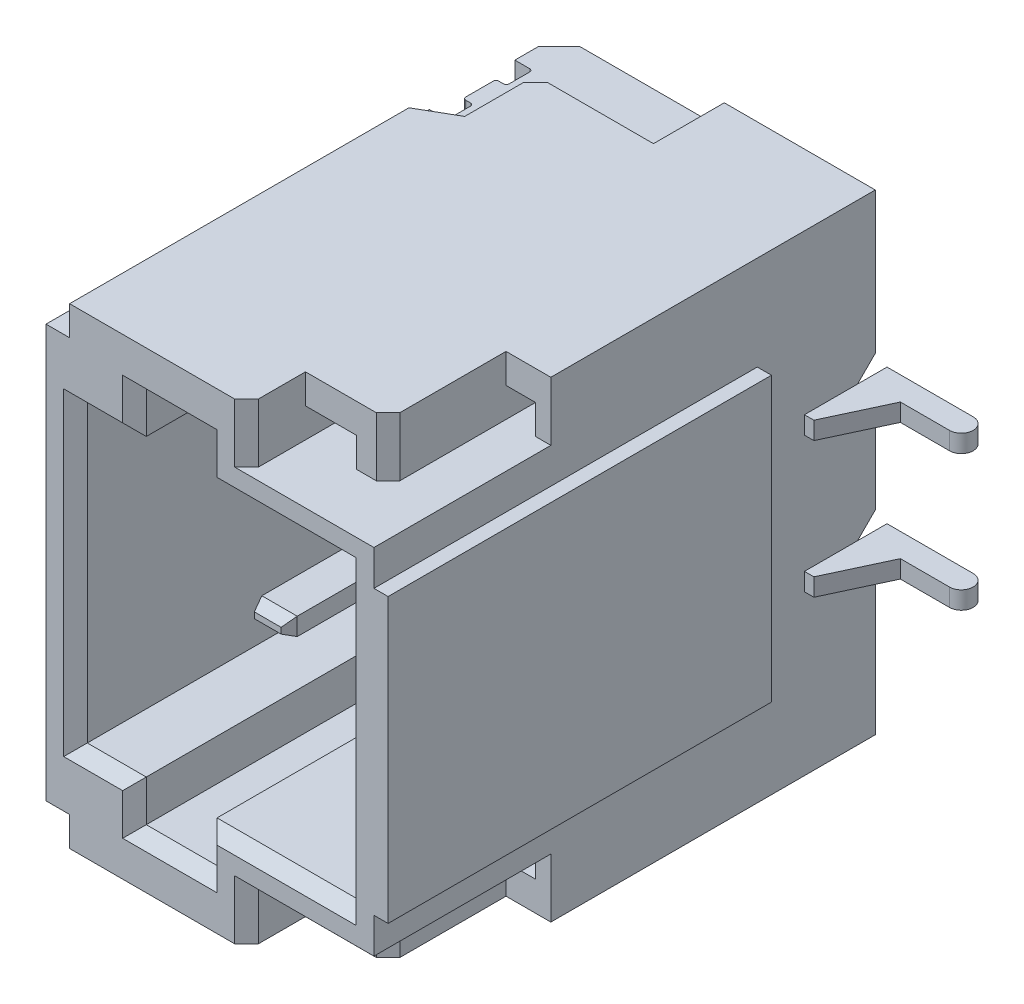
SolidWorks part; units mm, degrees
ref_plane "Front Plane" through (0, 0, 0) normal (0, 0, 1) x (1, 0, 0)
ref_plane "Top Plane" through (0, 0, 0) normal (0, 1, 0) x (1, 0, 0)
ref_plane "Right Plane" through (0, 0, 0) normal (1, 0, 0) x (0, 0, -1)
sketch "Sketch2" plane through (0, 0, 0) normal (0, 1, 0) x (1, 0, 0)
  line L0 (22.6306, -2.3603) -> (22.6306, -1.9103)
  line L1 (22.6306, -1.9103) -> (25.4106, -1.9103)
  line L2 (25.4106, -1.9103) -> (25.4106, -1.6603)
  line L3 (25.4106, -1.6603) -> (26.1406, -1.6603)
  line L4 (26.1406, -1.8603) -> (25.7238, -1.8603)
  line L5 (25.7238, -1.8603) -> (25.4906, -2.3603)
  line L6 (25.4906, -2.3603) -> (22.6306, -2.3603)
  arc A0 (26.1406, -1.8603) -> (26.1406, -1.6603) centre (26.1406, -1.7603) ccw
extrude "Boss-Extrude2" add sketch "Sketch2" along normal blind 0.15 from offset 0.815 separate body contours L6 L0 L1 L2 L3 A0 L4 L5 offset against normal yes
sketch "Sketch3" plane through (0, 0, 0) normal (0, 1, 0) x (1, 0, 0)
  line L0 (22.7306, -2.9603) -> (24.1306, -2.9603)
  line L1 (24.1306, -2.9603) -> (24.1306, -1.8353)
  line L2 (24.1306, -1.8353) -> (23.9556, -1.6603)
  line L3 (23.9556, -1.6603) -> (22.8056, -1.6603)
  line L4 (22.8056, -1.6603) -> (22.6306, -1.8353)
  line L5 (22.6306, -1.8353) -> (22.6306, -2.0353)
  line L6 (22.6306, -2.0353) -> (22.7556, -2.0353)
  line L7 (22.7806, -2.2328) -> (22.7806, -2.0603)
  line L8 (22.6306, -2.7603) -> (22.6306, -2.8603)
  line L9 (22.6306, -2.8603) -> (22.7306, -2.9603)
  line L10 (22.6306, -2.7603) -> (22.7556, -2.7603)
  line L11 (22.7806, -2.7353) -> (22.7806, -2.5628)
  line L12 (22.7181, -2.5378) -> (22.7556, -2.5378)
  line L13 (22.6931, -2.2828) -> (22.6931, -2.5128)
  line L14 (22.7181, -2.2578) -> (22.7556, -2.2578)
  arc A0 (22.7556, -2.7603) -> (22.7806, -2.7353) centre (22.7556, -2.7353) ccw
  arc A1 (22.7806, -2.5628) -> (22.7556, -2.5378) centre (22.7556, -2.5628) ccw
  arc A2 (22.7181, -2.5378) -> (22.6931, -2.5128) centre (22.7181, -2.5128) cw
  arc A3 (22.7556, -2.0353) -> (22.7806, -2.0603) centre (22.7556, -2.0603) cw
  arc A4 (22.7556, -2.2578) -> (22.7806, -2.2328) centre (22.7556, -2.2328) ccw
  arc A5 (22.7181, -2.2578) -> (22.6931, -2.2828) centre (22.7181, -2.2828) ccw
extrude "Boss-Extrude3" add sketch "Sketch3" along normal blind 0.2 from offset 2.26 separate body contours L0 L1 L2 L3 L4 L5 L6 A3 L7 A4 L14 A5 L13 A2 L12 A1 L11 A0 L10 L8 L9
sketch "Sketch4" plane through (0, 0, 0) normal (0, 0, 1) x (1, 0, 0)
  line L0 (25.5306, -3.2409) -> (22.6306, -3.2409)
  line L1 (22.6306, -3.2409) -> (22.6306, 2.7591)
  line L2 (25.5306, 2.7591) -> (22.6306, 2.7591)
  line L3 (25.5306, -3.2409) -> (25.5306, 2.7591)
extrude "Boss-Extrude4" add sketch "Sketch4" along normal blind 4.25 from offset 1.76 separate body
sketch "Sketch6" plane through (25.5306, 0, 0) normal (1, 0, 0) x (0, 0, -1)
  line L0 (-2.7603, -2.4409) -> (-2.7603, 1.9591)
  line L1 (-2.7603, 1.9591) -> (-6.161, 1.9591)
  line L2 (-6.161, 1.9591) -> (-6.161, -2.4409)
  line L3 (-6.161, -2.4409) -> (-2.7603, -2.4409)
extrude "Cut-Extrude3" cut sketch "Sketch6" against normal blind 0.12 flip side to cut
sketch "Sketch7" plane through (0, 0, 6.01) normal (0, 0, 1) x (1, 0, 0)
  line L0 (22.8806, -2.4909) -> (25.1606, -2.4909)
  line L1 (25.1606, -2.4909) -> (25.1606, 2.0091)
  line L2 (25.1606, 2.0091) -> (22.8806, 2.0091)
  line L3 (22.8806, 2.0091) -> (22.8806, -2.4909)
extrude "Cut-Extrude4" cut sketch "Sketch7" against normal blind 3.2
sketch "Sketch8" plane through (0, 0, 6.01) normal (0, 0, 1) x (1, 0, 0)
  line L0 (23.3806, 2.0091) -> (23.9806, 2.0091)
  line L1 (23.9806, 2.0091) -> (23.9806, 2.3591)
  line L2 (23.9806, 2.3591) -> (23.3806, 2.3591)
  line L3 (23.3806, 2.3591) -> (23.3806, 2.0091)
  line L4 (23.3806, -2.4909) -> (23.9806, -2.4909)
  line L5 (23.9806, -2.4909) -> (23.9806, -2.8409)
  line L6 (23.9806, -2.8409) -> (23.3806, -2.8409)
  line L7 (23.3806, -2.8409) -> (23.3806, -2.4909)
extrude "Cut-Extrude6" cut sketch "Sketch8" against normal blind 2.6
chamfer "Chamfer1" distance 0.1 angle 45 12 edges at (22.8806, -0.2409, 6.01) (23.1306, -2.4909, 6.01) (23.3806, -2.6659, 6.01) (23.6806, -2.8409, 6.01) (23.9806, -2.6659, 6.01) (24.5706, -2.4909, 6.01) (25.1606, -0.2409, 6.01) (24.5706, 2.0091, 6.01) (23.9806, 2.1841, 6.01) (23.6806, 2.3591, 6.01) (23.3806, 2.1841, 6.01) (23.1306, 2.0091, 6.01)
sketch "Sketch9" plane through (0, 0, 0) normal (0, 1, 0) x (1, 0, 0)
  line L0 (23.3606, -2.8103) -> (23.6606, -2.8103)
  line L1 (23.6606, -2.8103) -> (23.6606, -4.9103)
  line L2 (23.6606, -4.9103) -> (23.6242, -5.0103)
  line L3 (23.6242, -5.0103) -> (23.397, -5.0103)
  line L4 (23.397, -5.0103) -> (23.3606, -4.9103)
  line L5 (23.3606, -4.9103) -> (23.3606, -2.8103)
extrude "Boss-Extrude5" add sketch "Sketch9" along normal blind 0.15 from offset 1.82 separate body offset against normal yes
chamfer "Chamfer2" distance 0.1 distance2 0.05 1 edges at (23.5106, -1.82, 5.0103) first distance on face at (23.5106, -1.82, 4.2436)
chamfer "Chamfer3" distance 0.05 distance2 0.1 1 edges at (23.5106, -1.67, 5.0103) first distance on face at (23.5106, -1.72, 5.0103)
sketch "Sketch10" plane through (22.6306, 0, 0) normal (-1, 0, 0) x (0, 0, 1)
  line L0 (6.0103, 2.5091) -> (6.0103, 2.7591)
  line L1 (6.0103, 2.7591) -> (1.4717, 2.7591)
  line L2 (1.4717, 2.7591) -> (1.4717, 2.5091)
  line L3 (1.4717, 2.5091) -> (6.0103, 2.5091)
  line L4 (6.0103, -3.2409) -> (6.0103, -2.9909)
  line L5 (6.0103, -2.9909) -> (1.2054, -2.9909)
  line L6 (1.2054, -2.9909) -> (1.2054, -3.2409)
  line L7 (1.2054, -3.2409) -> (6.0103, -3.2409)
extrude "Cut-Extrude7" cut sketch "Sketch10" against normal blind 0.2
sketch "Sketch11" plane through (0, -3.2409, 0) normal (0, -1, 0) x (1, 0, 0)
  line L0 (22.6306, 3.249) -> (23.1306, 2.9603)
  line L1 (23.1306, 2.9603) -> (23.1306, 2.3603)
  line L2 (23.1306, 2.3603) -> (24.1306, 2.3603)
  line L3 (24.1306, 2.3603) -> (24.1306, 1.6436)
  line L4 (24.1306, 1.6436) -> (22.6306, 1.6436)
  line L5 (22.6306, 1.6436) -> (22.6306, 3.249)
extrude "Cut-Extrude8" cut sketch "Sketch11" against normal blind 0.5
sketch "Sketch12" plane through (23.1306, 0, 0) normal (-1, 0, 0) x (0, 0, 1)
  line L0 (2.9603, -2.9909) -> (2.9603, -2.7409)
  line L1 (2.9603, -2.7409) -> (2.9603, -3.2409) construction
  line L2 (2.9603, -2.7409) -> (2.3603, -2.7409)
  line L3 (2.3603, -2.7409) -> (2.3603, -2.9909)
  line L4 (2.3603, -2.7409) -> (2.3603, -3.2409) construction
  line L5 (2.3603, -2.9909) -> (2.9603, -2.9909)
extrude "Cut-Extrude9" cut sketch "Sketch12" against normal up to surface (1 mm away) up to face at (24.1306, -2.9909, 2.0601)
chamfer "Chamfer4" distance 0.1 angle 45 1 edges at (22.6306, -2.7409, 2.5045)
chamfer "Chamfer5" distance 0.1 angle 45 1 edges at (23.1306, -3.1159, 2.3603)
ref_plane "Plane1" through (0, -0.2409, 0) normal (0, -1, 0) x (-1, 0, 0)
mirror "Mirror1" about plane through (0, -0.2409, 0) normal (0, -1, 0) of "Chamfer5", "Cut-Extrude8", "Chamfer4", "Cut-Extrude9"
mirror "Mirror2" about plane through (0, -0.2409, 0) normal (0, -1, 0) of bodies 128
sketch "Sketch13" plane through (0, -3.2409, 0) normal (0, -1, 0) x (1, 0, 0)
  line L0 (24.3306, 5.5103) -> (24.3306, 6.0696)
  line L1 (25.0306, 4.5103) -> (25.671, 4.5103)
  line L2 (25.0306, 4.5103) -> (25.0306, 5.5103)
  line L3 (24.3306, 5.5103) -> (25.0306, 5.5103)
  line L4 (25.671, 4.5103) -> (25.671, 6.0696)
  line L5 (25.671, 6.0696) -> (24.3306, 6.0696)
  point P0 (24.3306, 5.5103)
  point P1 (25.0306, 4.5103)
  point P8 (25.0306, 5.4103)
extrude "Cut-Extrude10" cut sketch "Sketch13" against normal blind 0.5
chamfer "Chamfer6" distance 0.1 angle 45 2 edges at (24.3306, -2.9909, 6.01) (25.0306, -2.9909, 5.5103)
sketch "Sketch14" plane through (0, 0, 5.5103) normal (0, 0, 1) x (1, 0, 0)
  line L0 (24.3306, -2.7409) -> (24.3306, -2.9909)
  line L1 (24.3306, -2.7409) -> (24.3306, -3.2409) construction
  line L2 (24.3306, -2.9909) -> (24.7617, -2.9909)
  line L3 (24.7617, -2.9909) -> (24.7617, -2.7409)
  line L4 (24.3306, -2.7409) -> (24.9306, -2.7409) construction
  line L5 (24.7617, -2.7409) -> (24.3306, -2.7409)
  line L6 (25.0306, -2.7409) -> (25.0306, -2.9909)
  line L7 (25.0306, -2.7409) -> (25.0306, -3.2409) construction
  line L8 (25.0306, -2.9909) -> (25.2818, -2.9909)
  line L9 (25.2818, -2.9909) -> (25.2818, -2.7409)
  line L10 (25.0306, -2.7409) -> (25.4106, -2.7409) construction
  line L11 (25.2818, -2.7409) -> (25.0306, -2.7409)
extrude "Cut-Extrude11" cut sketch "Sketch14" against normal blind 2
mirror "Mirror3" about plane through (0, -0.2409, 0) normal (0, -1, 0) of "Chamfer6", "Cut-Extrude10", "Cut-Extrude11"
sketch "Szkic1" plane through (22.6306, 0, 0) normal (-1, 0, 0) x (0, 0, 1)
  line L0 (1.76, -0.2409) -> (6.1352, -0.2409) construction
  line L1 (1.76, 2.1591) -> (1.76, -2.6409) construction
  line L3 (1.4476, -1.2409) -> (6.4476, -1.2409)
  line L4 (1.4476, -1.2409) -> (1.4476, 0.7591)
  line L5 (1.4476, 0.7591) -> (6.4476, 0.7591)
  line L6 (6.4476, -1.2409) -> (6.4476, 0.7591)
  line L7 (1.4476, -1.2409) -> (6.4476, 0.7591) construction
  line L8 (1.4476, 0.7591) -> (6.4476, -1.2409) construction
  point P4 (3.9476, -0.2409)
  dimension "D1" = 2
  dimension "D2" = 5
extrude "Wytnij-wyciągnięcie1" cut sketch "Szkic1" against normal through all
move or copy body "Obiekt-Przenieś/Kopiuj1" bodies to move or copy 147 128 copy no translate (0, -2, 0) parameters "D1"=0, "D2"=2, "D3"=0
combine bodies "Połącz1" operation type add bodies to combine 149 148
sketch "Sketch5" plane through (22.6306, 0, 0) normal (-1, 0, 0) x (0, 0, 1)
  line L0 (1.7603, -0.4409) -> (1.9103, -0.5909)
  line L1 (1.9103, -0.5909) -> (2.3603, -0.5909)
  line L2 (2.3603, -0.5909) -> (2.3603, -0.7409)
  line L3 (2.3603, -0.7409) -> (1.9103, -0.7409)
  line L4 (1.9103, -0.7409) -> (1.7603, -0.8909)
  line L6 (1.7603, -0.4409) -> (1.7527, -0.4409)
  line L7 (1.7527, -0.4409) -> (1.7527, -0.8909)
  line L8 (1.7527, -0.8909) -> (1.7603, -0.8909)
  line L9 (1.76, -1.2409) -> (2.7788, -1.2409) construction
  line L10 (1.76, 0.1591) -> (1.76, -2.6409) construction
  line L11 (2.3603, -0.7409) -> (2.3603, -1.7409) construction
  line L12 (1.7527, -2.0409) -> (1.7603, -2.0409)
  line L13 (1.7603, -1.5909) -> (1.7527, -1.5909)
  line L14 (2.3603, -1.8909) -> (1.9103, -1.8909)
  line L15 (1.7603, -1.5909) -> (1.9103, -1.7409)
  line L16 (1.9103, -1.7409) -> (2.3603, -1.7409)
  line L17 (2.3603, -1.7409) -> (2.3603, -1.8909)
  line L18 (1.9103, -1.8909) -> (1.7603, -2.0409)
  line L19 (1.7527, -1.5909) -> (1.7527, -2.0409)
  line L20 (2.3603, -0.815) -> (2.3603, -1.2409) construction
  point P21 (2.3603, -1.2409)
  point P26 (2.3603, -1.2409)
  dimension "D1" = 1
extrude "Wytnij-wyciągnięcie2" cut sketch "Sketch5" against normal through all contours L4 L8 L7 L6 L0 L1 L2 L3 | L19 L12 L18 L14 L17 L16 L15 L13
move or copy body "Obiekt-Przenieś/Kopiuj2" bodies to move or copy 124 copy no translate (0, 0.074, 0) parameters "D1"=0, "D2"=0.074, "D3"=0
pattern_linear "Szyk liniowy1" count 2 spacing 1.15 along (0, -1, 0) of bodies 153
pattern_linear "Szyk liniowy2" count 2 spacing 1.15 along (0, 1, 0) of bodies 135
